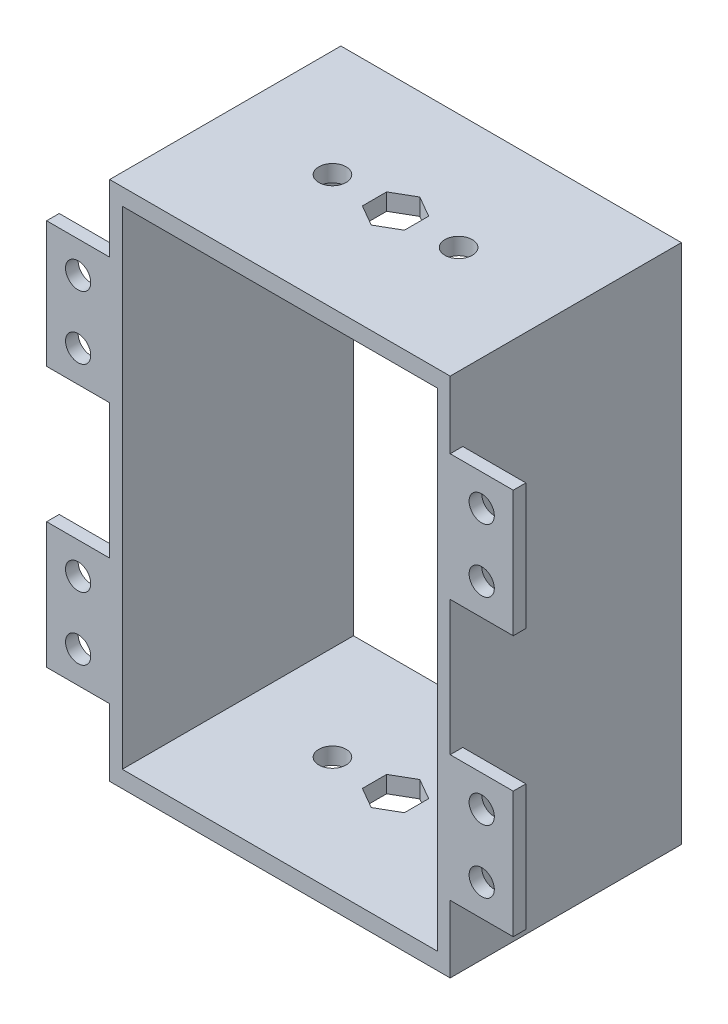
SolidWorks part; units mm, degrees
ref_plane "Front Plane" through (0, 0, 0) normal (0, 0, 1) x (1, 0, 0)
ref_plane "Top Plane" through (0, 0, 0) normal (0, 1, 0) x (1, 0, 0)
ref_plane "Right Plane" through (0, 0, 0) normal (1, 0, 0) x (0, 0, -1)
sketch "Sketch1" plane through (0, 0, 0) normal (0, 1, 0) x (1, 0, 0)
  line L0 (37.5, 55) -> (37.5, 0) construction
  line L1 (0, 0) -> (75, 0)
  line L2 (0, 0) -> (0, 55)
  line L3 (0, 55) -> (75, 55)
  line L4 (75, 0) -> (75, 55)
  line L5 (0, 27.5) -> (37.5, 27.5) construction
  line L6 (37.5, 27.5) -> (75, 27.5) construction
  line L8 (37.5, 33.2735) -> (32.5, 30.3868)
  line L9 (32.5, 30.3868) -> (32.5, 24.6132)
  line L10 (32.5, 24.6132) -> (37.5, 21.7265)
  line L11 (37.5, 21.7265) -> (42.5, 24.6132)
  line L12 (42.5, 24.6132) -> (42.5, 30.3868)
  line L13 (42.5, 30.3868) -> (37.5, 33.2735)
  circle A2 centre (37.5, 27.5) radius 10 construction
  circle A5 centre (22.5, 27.5) radius 3.25
  circle A6 centre (52.5, 27.5) radius 3.25
  circle A7 centre (37.5, 27.5) radius 5 construction
  dimension "D2" = 6.5
  dimension "D3" = 20
  dimension "D1" = 55
  dimension "D4" = 75
  dimension "D5" = 15
  dimension "D6" = 10
extrude "Boss-Extrude1" add sketch "Sketch1" along normal blind 4
sketch "Sketch2" plane through (0, 0, 0) normal (-1, 0, 0) x (0, 0, 1)
  line L0 (-55, 4) -> (-55, 0) construction
  line L1 (0, 0) -> (-55, 0)
  line L2 (0, 0) -> (0, 120)
  line L3 (0, 120) -> (-55, 120)
  line L4 (-55, 0) -> (-55, 120)
  dimension "D1" = 120
extrude "Boss-Extrude2" add sketch "Sketch2" along normal blind 3
ref_plane "Plane1" through (37.5, 0, 0) normal (1, 0, 0) x (0, 0, -1)
mirror "Mirror1" about plane through (37.5, 0, 0) normal (1, 0, 0) of "Boss-Extrude2"
sketch "Sketch3" plane through (0, 120, 0) normal (0, 1, 0) x (1, 0, 0)
  line L0 (42.5, 24.6132) -> (42.5, 30.3868) construction
  line L1 (-3, 0) -> (78, 0)
  line L2 (-3, 0) -> (-3, 55)
  line L3 (-3, 55) -> (78, 55)
  line L4 (78, 0) -> (78, 55)
  line L5 (37.5, 33.2735) -> (32.5, 30.3868)
  line L6 (32.5, 30.3868) -> (32.5, 24.6132)
  line L7 (32.5, 24.6132) -> (37.5, 21.7265)
  line L8 (37.5, 21.7265) -> (42.5, 24.6132)
  line L9 (42.5, 24.6132) -> (42.5, 30.3868)
  line L10 (42.5, 30.3868) -> (37.5, 33.2735)
  line L11 (42.5, 30.3868) -> (37.5, 33.2735) construction
  line L12 (37.5, 33.2735) -> (32.5, 30.3868) construction
  circle A2 centre (22.5, 27.5) radius 3.25
  circle A3 centre (22.5, 27.5) radius 3.25 construction
  circle A4 centre (52.5, 27.5) radius 3.25
  circle A5 centre (52.5, 27.5) radius 3.25 construction
  circle A6 centre (37.5, 27.5) radius 5 construction
extrude "Boss-Extrude3" add sketch "Sketch3" along normal blind 4
sketch "Sketch5" plane through (0, 0, 0) normal (0, 0, 1) x (1, 0, 0)
  line L0 (78, 62) -> (-3, 62) construction
  line L1 (78, 0) -> (78, 124) construction
  line L2 (-3, 0) -> (-3, 124) construction
  line L3 (78, 124) -> (-3, 62) construction
  line L4 (-3, 78) -> (-18, 78)
  line L5 (-3, 78) -> (-3, 108)
  line L6 (-3, 108) -> (-18, 108)
  line L7 (-18, 78) -> (-18, 108)
  line L8 (-3, 108) -> (-18, 93) construction
  line L9 (-18, 93) -> (-3, 93) construction
  line L10 (-3, 16) -> (-18, 16)
  line L11 (-18, 46) -> (-18, 16)
  line L12 (-3, 46) -> (-18, 46)
  line L13 (-3, 46) -> (-3, 16)
  circle A0 centre (-10.5, 100.5) radius 3
  circle A1 centre (-10.5, 85.5) radius 3
  circle A2 centre (-10.5, 38.5) radius 3
  circle A3 centre (-10.5, 23.5) radius 3
  point P11 (37.5, 93)
  point P13 (-3, 93)
  dimension "D3" = 6
  dimension "D1" = 15
  dimension "D2" = 30
extrude "Boss-Extrude5" add sketch "Sketch5" against normal blind 3
mirror "Mirror2" about plane through (37.5, 0, 0) normal (1, 0, 0) of "Boss-Extrude5"
equation "\"length\"=120"
equation "\"D1@Sketch2\"=\"length\""
equation "\"D3@LPattern1\"=\"length\""
